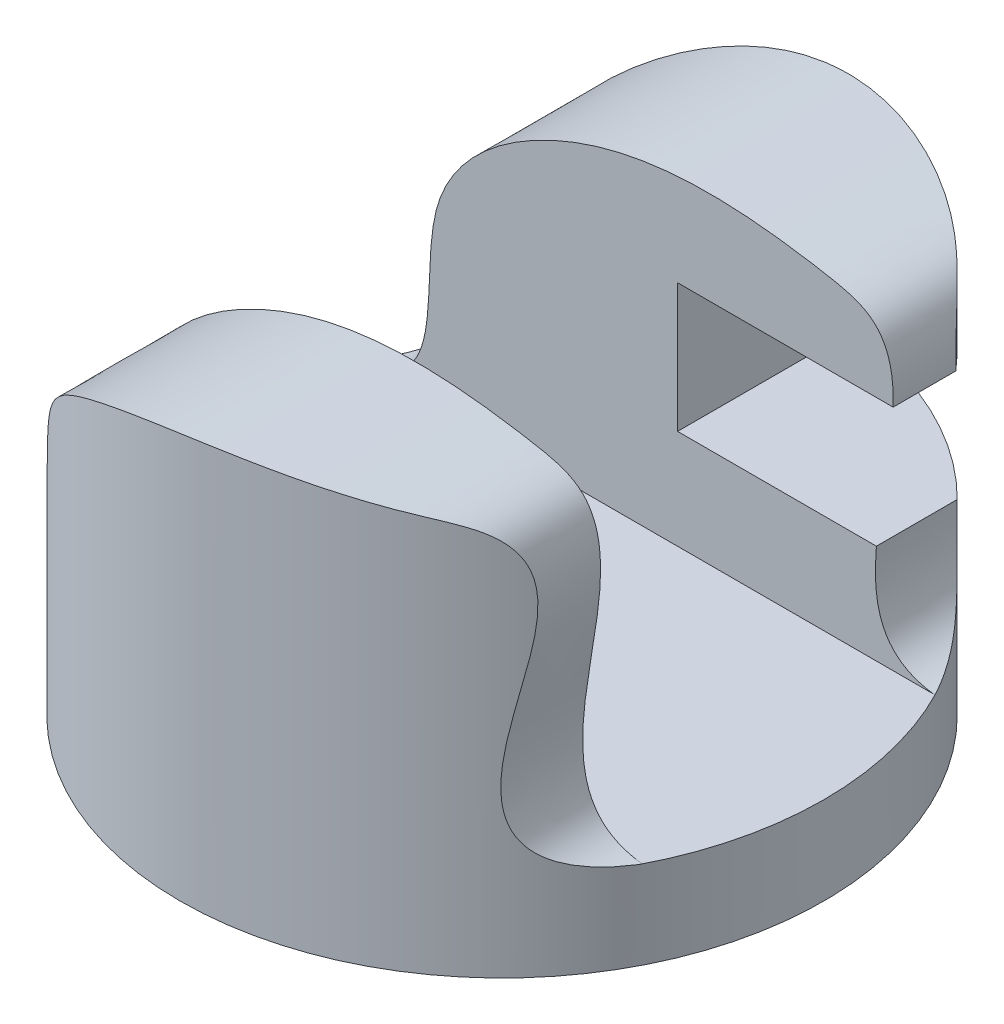
SolidWorks part; units mm, degrees
ref_plane "Front Plane" through (0, 0, 0) normal (0, 0, 1) x (1, 0, 0)
ref_plane "Top Plane" through (0, 0, 0) normal (0, 1, 0) x (1, 0, 0)
ref_plane "Right Plane" through (0, 0, 0) normal (1, 0, 0) x (0, 0, -1)
sketch "Sketch1" plane through (0, 0, 0) normal (0, 1, 0) x (1, 0, 0)
  circle A0 centre (0, 0) radius 55
  dimension "D1" = 110
extrude "Boss-Extrude1" add sketch "Sketch1" along normal blind 80
sketch "Sketch5" plane through (0, 0, 0) normal (0, 1, 0) x (1, 0, 0)
  line L1 (55.3407, -25) -> (-55.3407, -25)
  line L2 (55.3407, -25) -> (55.3407, 25)
  line L3 (55.3407, 25) -> (-55.3407, 25)
  line L4 (-55.3407, -25) -> (-55.3407, 25)
  line L5 (55.3407, -25) -> (-55.3407, 25) construction
  line L6 (55.3407, 25) -> (-55.3407, -25) construction
  point P0 (0, 0)
  dimension "D1" = 50
extrude "Cut-Extrude2" cut sketch "Sketch5" along normal blind 85 from offset 15
sketch "Sketch4" plane through (0, 0, 0) normal (0, 0, 1) x (1, 0, 0)
  line L0 (-55, 15) -> (55, 15)
  line L5 (-55, 0) -> (55, 0) construction
  line L6 (55, 80) -> (-55, 80) construction
  line L7 (-55, 15) -> (-94.8282, 60.4525)
  line L8 (-94.8282, 60.4525) -> (-52.2656, 84.774)
  line L9 (-52.2656, 84.774) -> (65.61, 86.1787)
  line L10 (65.61, 86.1787) -> (71.585, 38.1442)
  line L11 (71.585, 38.1442) -> (55, 15)
  line L15 (-55, 15) -> (-55, 0) construction
  line L16 (-55, 15) -> (-55, 0)
  line L17 (55, 0) -> (55, 15) construction
  line L18 (55, 0) -> (55, 15)
  line L19 (48.9898, 80) -> (48.9898, 15) construction
  line L20 (-48.9898, 15) -> (-48.9898, 80) construction
  spline S0 degree 3 poles (-55, 15) (-31.7624, 13.3309) (-45.7599, 45.0444) (-10.2587, 71.3903) (16.6588, 70.7317) (56.6638, 62.711) (21.5379, 11.6598) (55, 15) knots 0 0 0 0 0.221887 0.380112 0.626066 0.665786 1 1 1 1
  point P0 (-55, 15)
  point P2 (-35.9898, 45)
  point P9 (-38.9898, 22)
  point P10 (-14.9898, 65)
  point P11 (29.9898, 68)
  point P27 (55, 15.3792)
  point P28 (-55, 15.048)
  point P29 (-55, 15)
  point P30 (-54.992, 15)
  dimension "D1" = 15
  dimension "D2" = 15
  dimension "D3" = 7
  dimension "D4" = 12
  dimension "D5" = 30
  dimension "D6" = 19
  dimension "D7" = 50
  dimension "D8" = 12
  dimension "D9" = 34
  dimension "D10" = 14
  dimension "D11" = 13
  dimension "D12" = 10
  dimension "D14" = 6
extrude "Cut-Extrude1" cut sketch "Sketch4" against normal through all both and the other way through all contours L7 S0 L11 L10 L9 L8 region at (-73.5528, 38.9191, 0)
sketch "Sketch6" plane through (0, 0, 25) normal (0, 0, -1) x (-1, 0, 0)
  line L0 (48.9898, 15) -> (-48.8004, 15) construction
  circle A0 centre (-18, 43) radius 11.2
  dimension "D1" = 22.4
  dimension "D2" = 18
  dimension "D3" = 28
extrude "Cut-Extrude3" cut sketch "Sketch6" against normal blind 8
sketch "Sketch7" plane through (0, 0, -25) normal (0, 0, 1) x (1, 0, 0)
  line L0 (48.8004, 15) -> (-48.9898, 15) construction
  line L1 (46.2118, 32) -> (5, 32)
  line L2 (46.2118, 32) -> (46.2118, 54)
  line L3 (46.2118, 54) -> (5, 54)
  line L4 (5, 32) -> (5, 54)
  line L5 (46.2118, 32) -> (5, 54) construction
  line L6 (46.2118, 54) -> (5, 32) construction
  point P0 (25.6059, 43)
  point P5 (18, 43)
  point P6 (0, 0)
  point P8 (0, 0)
  point P9 (0, 0)
  point P10 (27.8322, 15.6109)
  dimension "D1" = 13
  dimension "D2" = 18
  dimension "D3" = 28
  dimension "D4" = 22
extrude "Cut-Extrude4" cut sketch "Sketch7" against normal blind 48
